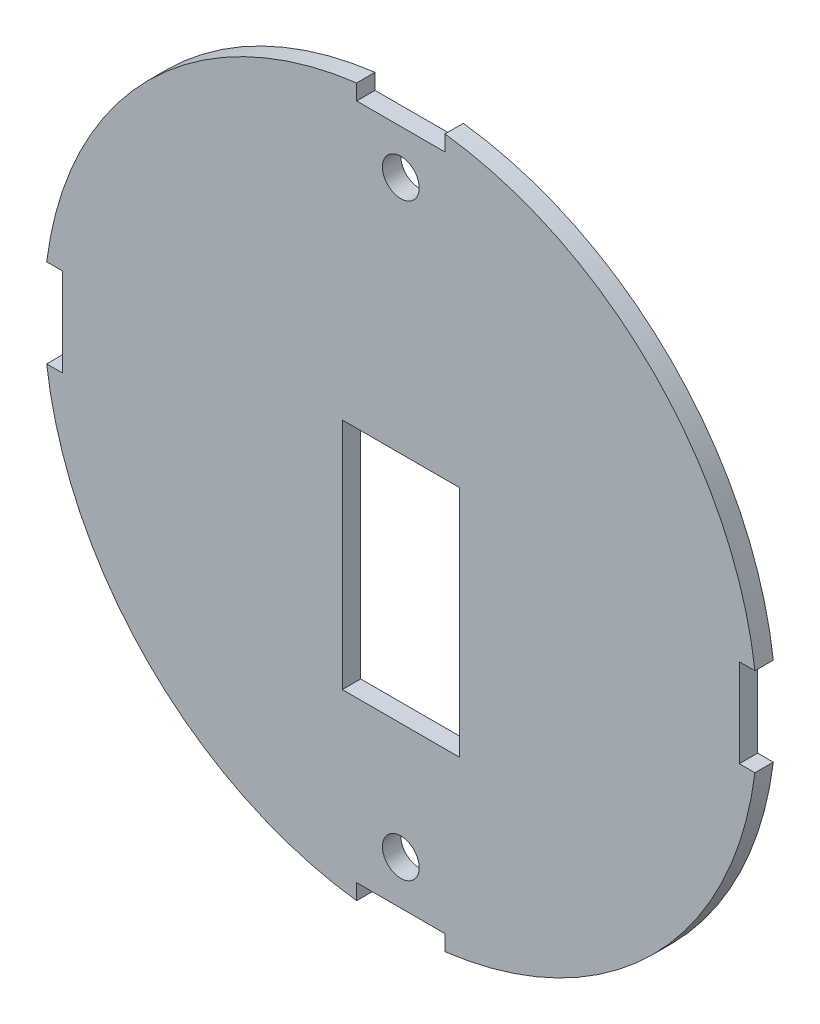
SolidWorks part; units mm, degrees
material "A-Glass Fiber"
ref_plane "Front Plane" through (0, 0, 0) normal (0, 0, 1) x (1, 0, 0)
ref_plane "Top Plane" through (0, 0, 0) normal (0, 1, 0) x (1, 0, 0)
ref_plane "Right Plane" through (0, 0, 0) normal (1, 0, 0) x (0, 0, -1)
sketch "Sketch1" plane through (0, 0, 0) normal (0, 0, 1) x (1, 0, 0)
  circle A0 centre (0, 0) radius 61.595
extrude "Boss-Extrude1" add sketch "Sketch1" along normal blind 3.175
sketch "Sketch2" plane through (0, 0, 3.175) normal (0, 0, 1) x (1, 0, 0)
  line L0 (0, 0) -> (0, 61.595) construction
  line L2 (-7.62, 58.42) -> (7.62, 58.42)
  line L3 (-7.62, 58.42) -> (-7.62, 64.77)
  line L4 (-7.62, 64.77) -> (7.62, 64.77)
  line L5 (7.62, 58.42) -> (7.62, 64.77)
  line L6 (-7.62, 58.42) -> (7.62, 64.77) construction
  line L7 (-7.62, 64.77) -> (7.62, 58.42) construction
  circle A0 centre (0, 0) radius 61.595 construction
  circle A1 centre (0, 50.8) radius 3.175
  dimension "D3" = 50.8
  dimension "D1" = 15.24
  dimension "D2" = 6.35
extrude "Cut-Extrude1" cut sketch "Sketch2" against normal blind 3.175 contours L5 L4 L3 L2 | A1
pattern_circular "CirPattern1" count 4 every 90 about axis through (0, 0, 3.175) along (0, 0, 1) of "Cut-Extrude1"
sketch "Sketch3" plane through (0, 0, 3.175) normal (0, 0, 1) x (1, 0, 0)
  line L2 (-10.1, 9.5) -> (-10.1, -29.8)
  line L3 (10.1, 9.5) -> (-10.1, 9.5)
  line L6 (10.1, -29.8) -> (10.1, 8.5)
  line L7 (-9.1, -30.8) -> (9.1, -30.8)
  line L8 (-9.1, -30.8) -> (-10.1, -30.8)
  line L9 (-10.1, -30.8) -> (-10.1, -29.8)
  line L10 (9.1, -30.8) -> (10.1, -30.8)
  line L11 (10.1, -30.8) -> (10.1, -29.8)
  line L12 (10.1, 8.5) -> (10.1, 9.5)
extrude "Cut-Extrude2" cut sketch "Sketch3" against normal blind 3.175
sketch "Sketch4" plane through (0, 0, 0) normal (0, 0, -1) x (-1, 0, 0)
  circle A0 centre (5, -34.65) radius 2.413
  circle A1 centre (-5, -34.65) radius 2.413
  circle A2 centre (-5, 13.35) radius 2.413
  circle A3 centre (5, 13.35) radius 2.413
extrude "Cut-Extrude3" [suppressed] cut sketch "Sketch4" against normal blind 3.175
sketch "Sketch5" plane through (0, 0, 0) normal (0, 0, -1) x (-1, 0, 0)
  circle A0 centre (-50.8, 0) radius 3.175
  circle A1 centre (50.8, 0) radius 3.175
extrude "Boss-Extrude2" add sketch "Sketch5" against normal blind 3.175
sketch "Sketch6" plane through (0, 0, 3.175) normal (0, 0, 1) x (1, 0, 0)
  line L0 (0, 58.42) -> (0, -58.42) construction
  line L1 (-7.62, 58.42) -> (7.62, 58.42) construction
  line L2 (7.62, -58.42) -> (-7.62, -58.42) construction
  circle A0 centre (16.3543, 40.8119) radius 1.4732 construction
  circle A1 centre (35.4043, 40.8119) radius 1.4732 construction
  circle A2 centre (35.4043, -40.8119) radius 1.4732 construction
  circle A3 centre (16.3543, -40.8119) radius 1.4732 construction
  circle A4 centre (16.3543, 40.8119) radius 1.4732
  circle A5 centre (35.4043, 40.8119) radius 1.4732
  circle A6 centre (35.4043, -40.8119) radius 1.4732
  circle A7 centre (16.3543, -40.8119) radius 1.4732
  circle A8 centre (-16.3543, -40.8119) radius 1.4732
  circle A9 centre (-35.4043, -40.8119) radius 1.4732
  circle A10 centre (-35.4043, 40.8119) radius 1.4732
  circle A11 centre (-16.3543, 40.8119) radius 1.4732
extrude "Cut-Extrude4" [suppressed] cut sketch "Sketch6" against normal through all
